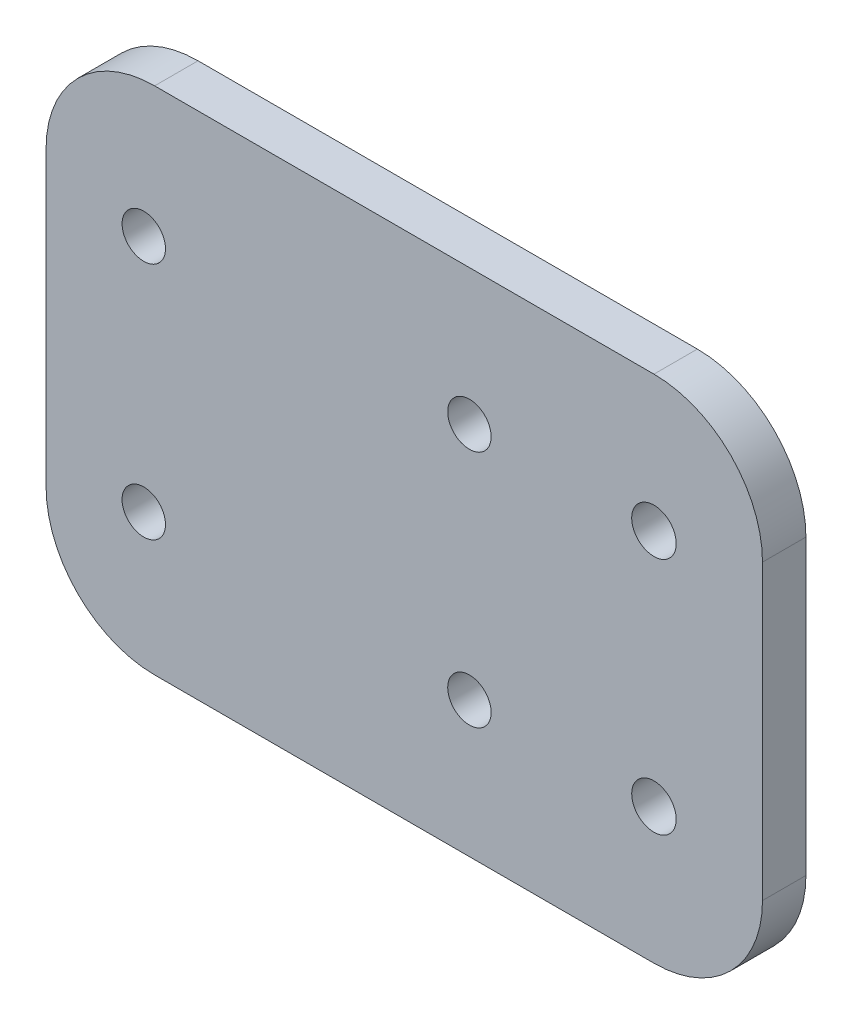
SolidWorks part; units mm, degrees
material "A-玻璃纤维"
ref_plane "前视基准面" through (0, 0, 0) normal (0, 0, 1) x (1, 0, 0)
ref_plane "上视基准面" through (0, 0, 0) normal (0, 1, 0) x (1, 0, 0)
ref_plane "右视基准面" through (0, 0, 0) normal (1, 0, 0) x (0, 0, -1)
other "Configuration Table"
sketch "草图1" plane through (0, 0, 0) normal (0, 0, 1) x (1, 0, 0)
  line L1 (0, 0) -> (66, 0)
  line L2 (0, 0) -> (0, 47)
  line L3 (0, 47) -> (66, 47)
  line L4 (66, 0) -> (66, 47)
  dimension "D1" = 66
  dimension "D2" = 47
extrude "凸台-拉伸1" add sketch "草图1" along normal blind 4
fillet "圆角1" radius 10 4 edges at (0, 47, 2) (66, 0, 2) (0, 0, 2) (66, 47, 2)
sketch "草图2" plane through (0, 0, 4) normal (0, 0, 1) x (1, 0, 0)
  line L0 (0, 37) -> (0, 10) construction
  line L1 (0, 23.5) -> (85.3311, 23.5) construction
  line L2 (30, 23.5) -> (115.3311, 23.5) construction
  line L3 (66, 10) -> (66, 37) construction
  circle A0 centre (9, 34.5) radius 2
  circle A1 centre (9, 12.5) radius 2
  circle A2 centre (39, 34.5) radius 2
  circle A3 centre (39, 12.5) radius 2
  circle A4 centre (56, 34.5) radius 2.05
  circle A5 centre (56, 12.5) radius 2.05
  dimension "D1" = 4
  dimension "D3" = 22
  dimension "D5" = 30
  dimension "D6" = 4.1
  dimension "D7" = 22
  dimension "D8" = 10
  dimension "D2" = 9
  dimension "D4" = 2
extrude "切除-拉伸1" cut sketch "草图2" against normal blind 4
